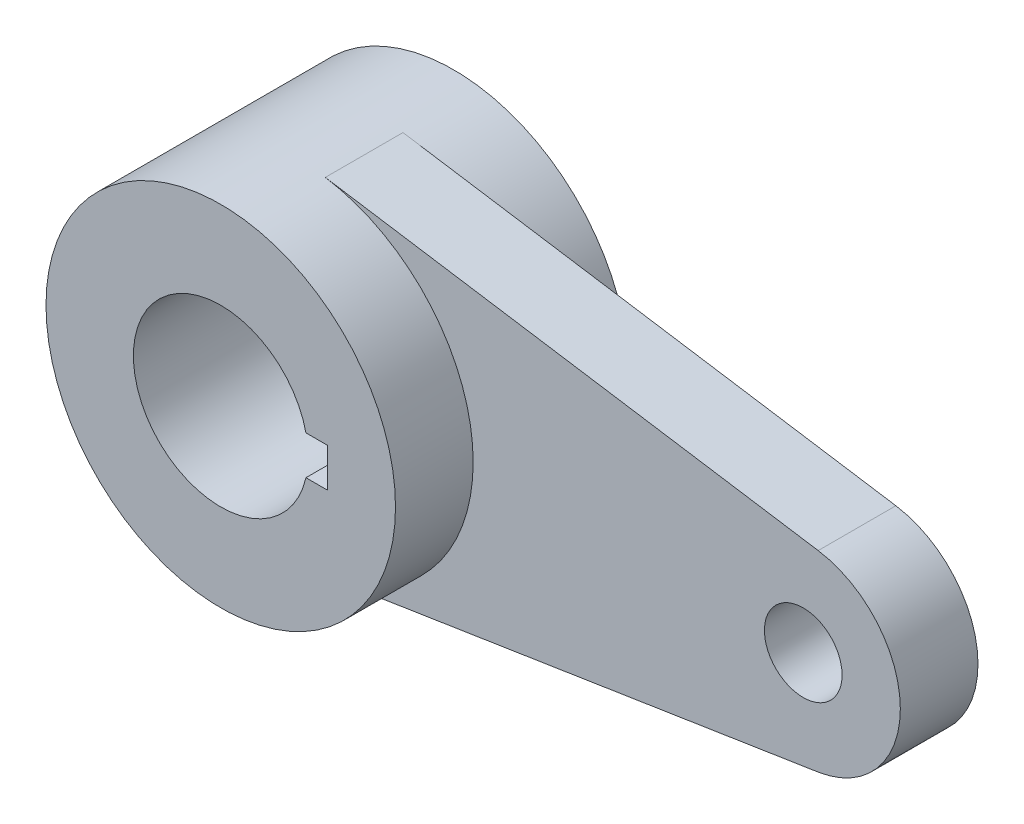
SolidWorks part; units mm, degrees
ref_plane "Front Plane" through (0, 0, 0) normal (0, 0, 1) x (1, 0, 0)
ref_plane "Top Plane" through (0, 0, 0) normal (0, 1, 0) x (1, 0, 0)
ref_plane "Right Plane" through (0, 0, 0) normal (1, 0, 0) x (0, 0, -1)
sketch "Sketch1" plane through (0, 0, 0) normal (0, 0, 1) x (1, 0, 0)
  line L0 (84.9923, 15.686) -> (4.3962, 28.2348)
  line L1 (4.3962, -28.2348) -> (84.9923, -15.686)
  circle A0 centre (0, 0) radius 28.575
  circle A1 centre (82.55, 0) radius 15.875
  point P3 (82.55, 0)
  dimension "D1" = 57.15
  dimension "D2" = 31.75
extrude "Boss-Extrude3" add sketch "Sketch1" along normal blind 6.35 and the other way blind 6.35 contours A1 L0 A0 L1 | A1 A0 region at (45.7817, 0, 0) region at (82.55, 0, 0)
sketch "Sketch3" plane through (0, 0, 0) normal (0, 0, 1) x (1, 0, 0)
  circle A0 centre (0, 0) radius 28.575
  dimension "D1" = 57.15
extrude "Boss-Extrude4" add sketch "Sketch3" along normal blind 19.05 and the other way blind 19.05
sketch "Sketch4" plane through (0, 0, 6.35) normal (0, 0, 1) x (1, 0, 0)
  circle A0 centre (82.55, 0) radius 6.35
  point P0 (82.55, 0)
  point P1 (82.55, 0)
  dimension "D1" = 12.7
extrude "Cut-Extrude1" cut sketch "Sketch4" against normal through all
sketch "Sketch5" plane through (0, 0, 19.05) normal (0, 0, 1) x (1, 0, 0)
  circle A0 centre (0, 0) radius 14.2875
  dimension "D1" = 28.575
extrude "Cut-Extrude2" cut sketch "Sketch5" against normal through all
sketch "Sketch6" plane through (0, 0, 19.05) normal (0, 0, 1) x (1, 0, 0)
  line L1 (0, 3.175) -> (17.4752, 3.175)
  line L2 (0, 3.175) -> (0, -3.175)
  line L3 (0, -3.175) -> (17.4752, -3.175)
  line L4 (17.4752, 3.175) -> (17.4752, -3.175)
  dimension "D1" = 17.4752
  dimension "D2" = 6.35
extrude "Cut-Extrude3" cut sketch "Sketch6" against normal through all
